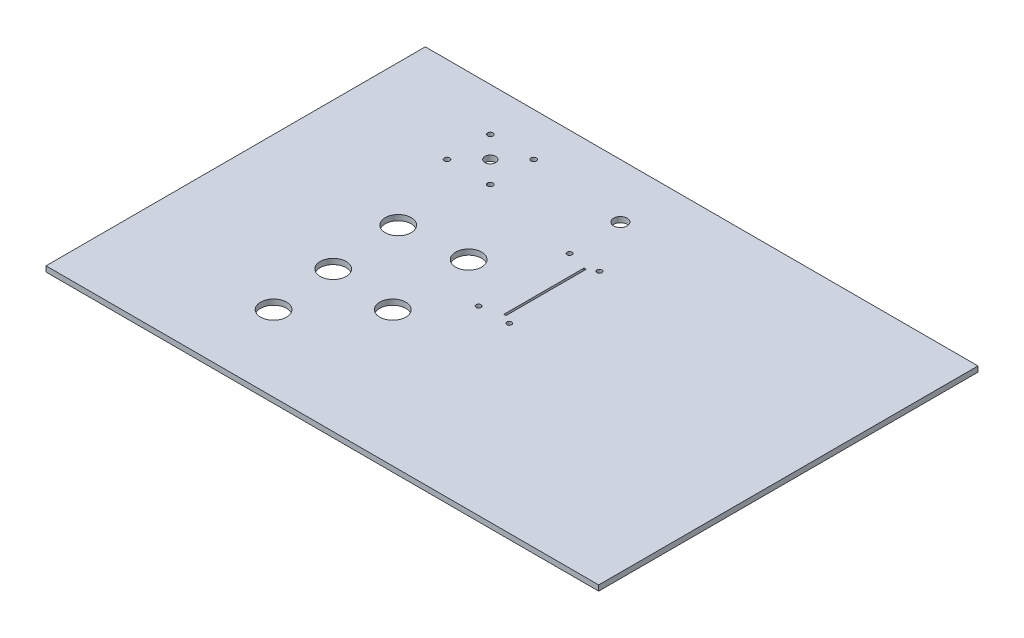
SolidWorks part; units mm, degrees
material "Perspex (TM) GS Acrylic Cast Sheet"
ref_plane "Front Plane" through (0, 0, 0) normal (0, 0, 1) x (1, 0, 0)
ref_plane "Top Plane" through (0, 0, 0) normal (0, 1, 0) x (1, 0, 0)
ref_plane "Right Plane" through (0, 0, 0) normal (1, 0, 0) x (0, 0, -1)
sketch "Sketch1" plane through (0, 0, 0) normal (0, 1, 0) x (1, 0, 0)
  line L1 (0, 0) -> (510, 0)
  line L2 (0, 0) -> (0, 350)
  line L3 (0, 350) -> (510, 350)
  line L4 (510, 0) -> (510, 350)
  dimension "D1" = 510
  dimension "D2" = 350
extrude "Boss-Extrude1" add sketch "Sketch1" along normal blind 5
sketch "Sketch2" plane through (0, 5, 0) normal (0, 1, 0) x (1, 0, 0)
  line L0 (510, 350) -> (0, 350) construction
  line L1 (120, 290) -> (185.8433, 290) construction
  line L2 (120, 290) -> (120, 336.2555) construction
  line L3 (0, 350) -> (0, 0) construction
  circle A0 centre (120, 290) radius 5
  circle A2 centre (140, 310) radius 2.5
  circle A3 centre (140, 270) radius 2.5
  circle A4 centre (100, 270) radius 2.5
  circle A5 centre (100, 310) radius 2.5
  dimension "D1" = 10
  dimension "D2" = 60
  dimension "D5" = 5
  dimension "D3" = 20
  dimension "D4" = 20
  dimension "D6" = 120
extrude "Joyystick1" cut sketch "Sketch2" against normal through all
sketch "Sketch3" plane through (0, 5, 0) normal (0, 1, 0) x (1, 0, 0)
  line L0 (0, 350) -> (0, 0) construction
  line L1 (510, 350) -> (0, 350) construction
  circle A0 centre (130, 195) radius 12
  circle A1 centre (190, 200) radius 12
  circle A2 centre (135, 130) radius 12
  circle A3 centre (195, 125) radius 12
  circle A4 centre (140, 70) radius 12
  dimension "D1" = 24
  dimension "D2" = 24
  dimension "D3" = 24
  dimension "D4" = 24
  dimension "D5" = 24
  dimension "D6" = 130
  dimension "D7" = 135
  dimension "D8" = 140
  dimension "D9" = 190
  dimension "D10" = 195
  dimension "D11" = 150
  dimension "D12" = 155
  dimension "D13" = 225
  dimension "D14" = 220
  dimension "D15" = 280
extrude "buttons1" cut sketch "Sketch3" against normal through all
sketch "Sketch4" plane through (0, 5, 0) normal (0, 1, 0) x (1, 0, 0)
  line L0 (510, 350) -> (0, 350) construction
  line L1 (0, 350) -> (0, 0) construction
  circle A0 centre (230, 300) radius 6.25
  dimension "D1" = 12.5
  dimension "D2" = 50
  dimension "D3" = 230
extrude "rocket Switch" cut sketch "Sketch4" against normal through all
sketch "Sketch5" plane through (0, 5, 0) normal (0, 1, 0) x (1, 0, 0)
  line L0 (252, 209.4006) -> (210.2533, 209.4006) construction
  line L1 (250, 246.4006) -> (252, 246.4006)
  line L2 (250, 246.4006) -> (250, 172.4006)
  line L3 (250, 172.4006) -> (252, 172.4006)
  line L4 (252, 246.4006) -> (252, 172.4006)
  line L5 (250, 209.4006) -> (252, 209.4006) construction
  line L7 (510, 350) -> (0, 350) construction
  line L8 (245.7526, 253.6631) -> (244.4144, 159.4144) construction
  line L9 (0, 350) -> (0, 0) construction
  circle A0 centre (231.719, 251.4006) radius 2.25
  circle A1 centre (259.7162, 251.0031) radius 2.25
  circle A2 centre (259.7162, 167.7981) radius 2.25
  circle A3 centre (231.719, 167.4006) radius 2.25
  point P7 (251, 246.4006)
  dimension "D5" = 4.5
  dimension "D1" = 2
  dimension "D2" = 74
  dimension "D3" = 5.35
  dimension "D4" = 250
  dimension "D6" = 14
  dimension "D7" = 140.5994
  dimension "D8" = 5
extrude "Cut-Extrude4" cut sketch "Sketch5" against normal through all
